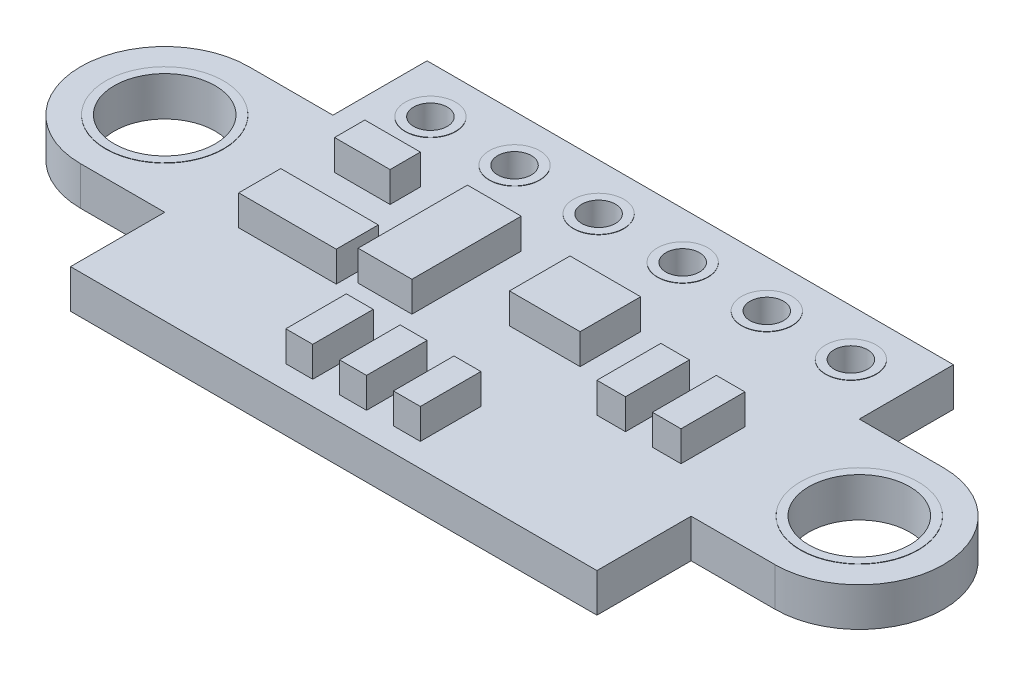
SolidWorks part; units mm, degrees
material "Copper"
ref_plane "Front Plane" through (0, 0, 0) normal (0, 0, 1) x (1, 0, 0)
ref_plane "Top Plane" through (0, 0, 0) normal (0, 1, 0) x (1, 0, 0)
ref_plane "Right Plane" through (0, 0, 0) normal (1, 0, 0) x (0, 0, -1)
sketch "Sketch1" plane through (0, 0, 0) normal (0, 1, 0) x (1, 0, 0)
  line L5 (-7.825, -5.3) -> (7.825, -5.3)
  line L6 (-7.825, -5.3) -> (-7.825, -2.5)
  line L7 (-7.825, 5.3) -> (7.825, 5.3)
  line L8 (7.825, -5.3) -> (7.825, -2.5)
  line L11 (10.325, 2.5) -> (7.825, 2.5)
  line L12 (10.325, -2.5) -> (7.825, -2.5)
  line L13 (-10.325, 2.5) -> (-7.825, 2.5)
  line L14 (-10.325, -2.5) -> (-7.825, -2.5)
  line L15 (-7.825, 2.5) -> (-7.825, 5.3)
  line L16 (7.825, 2.5) -> (7.825, 5.3)
  arc A0 (10.325, -2.5) -> (10.325, 2.5) centre (10.325, 0) ccw
  arc A1 (-10.325, -2.5) -> (-10.325, 2.5) centre (-10.325, 0) cw
  circle A2 centre (-10.325, 0) radius 1.5
  circle A3 centre (10.325, 0) radius 1.5
  point P0 (0, 0)
  dimension "D4" = 5
  dimension "D1" = 3
  dimension "D2" = 5
  dimension "D3" = 15.65
  dimension "D5" = 10.6
extrude "PCB" add sketch "Sketch1" along normal blind 1.15
sketch "Sketch2" plane through (0, 1.15, 0) normal (0, 1, 0) x (1, 0, 0)
  line L0 (-7.825, 3.9) -> (7.825, 3.9) construction
  line L1 (-7.825, 5.3) -> (-7.825, 2.5) construction
  line L2 (7.825, 2.5) -> (7.825, 5.3) construction
  circle A0 centre (-6.325, 3.9) radius 0.5
  dimension "D1" = 1
  dimension "D2" = 1.5
extrude "Initial Hole" cut sketch "Sketch2" against normal through all
pattern_linear "Pin Hole LPattern" count 6 spacing 2.5 along (1, 0, 0) of "Initial Hole"
sketch "Sketch4" plane through (0, 0, 0) normal (0, -1, 0) x (1, 0, 0)
  line L0 (-7.825, 2.5) -> (-7.825, 5.3) construction
  line L1 (-2.325, 3.7) -> (2.075, 3.7)
  line L2 (-2.325, 3.7) -> (-2.325, 1.3)
  line L3 (-2.325, 1.3) -> (2.075, 1.3)
  line L4 (2.075, 3.7) -> (2.075, 1.3)
  line L5 (-7.825, 5.3) -> (7.825, 5.3) construction
  dimension "D1" = 2.4
  dimension "D2" = 4.4
  dimension "D3" = 5.5
  dimension "D4" = 1.6
extrude "Bottom Component" add sketch "Sketch4" along normal blind 0.7
sketch "Sketch3" plane through (0, 1.15, 0) normal (0, 1, 0) x (1, 0, 0)
  line L0 (-1.325, -4.6) -> (-1.325, -2.8)
  line L1 (7.825, -5.3) -> (7.825, -2.5) construction
  line L2 (-6.325, -0.55) -> (-3.425, -0.55)
  line L3 (-6.325, -0.55) -> (-6.325, -1.8)
  line L4 (-6.325, -1.8) -> (-3.425, -1.8)
  line L5 (-2.125, -2.8) -> (-2.125, -4.6)
  line L6 (-3.425, -0.55) -> (-3.425, -1.8)
  line L7 (-2.125, -2.8) -> (-1.325, -2.8)
  line L8 (-2.125, -4.6) -> (-1.325, -4.6)
  line L9 (-7.825, -5.3) -> (7.825, -5.3) construction
  line L10 (-7.825, -2.5) -> (-7.825, -5.3) construction
  line L11 (-1.325, -2.8) -> (-0.525, -2.8) construction
  line L12 (0.275, -2.8) -> (1.075, -2.8) construction
  line L13 (-0.525, -2.8) -> (0.275, -2.8)
  line L14 (-0.525, -2.8) -> (-0.525, -4.6)
  line L15 (-0.525, -4.6) -> (0.275, -4.6)
  line L16 (0.275, -2.8) -> (0.275, -4.6)
  line L17 (-3.125, 1.8) -> (-1.525, 1.8)
  line L18 (1.075, -2.8) -> (1.875, -2.8)
  line L19 (1.075, -2.8) -> (1.075, -4.6)
  line L20 (1.075, -4.6) -> (1.875, -4.6)
  line L21 (1.875, -2.8) -> (1.875, -4.6)
  line L22 (-6.325, 1.95) -> (-4.675, 1.95)
  line L23 (-6.325, 1.95) -> (-6.325, 1.05)
  line L24 (-6.325, 1.05) -> (-4.675, 1.05)
  line L25 (-4.675, 1.95) -> (-4.675, 1.05)
  line L26 (-3.125, 1.8) -> (-3.125, -1.45)
  line L27 (-3.125, -1.45) -> (-1.525, -1.45)
  line L28 (-1.525, 1.8) -> (-1.525, -1.45)
  line L29 (0.225, 1.5) -> (2.325, 1.5)
  line L30 (0.225, 1.5) -> (0.225, -0.3)
  line L31 (0.225, -0.3) -> (2.325, -0.3)
  line L32 (2.325, 1.5) -> (2.325, -0.3)
  line L33 (3.825, 0.6) -> (4.675, 0.6)
  line L34 (3.825, 0.6) -> (3.825, -1.3)
  line L35 (3.825, -1.3) -> (4.675, -1.3)
  line L36 (4.675, 0.6) -> (4.675, -1.3)
  line L37 (5.475, 0.6) -> (6.325, 0.6)
  line L38 (5.475, 0.6) -> (5.475, -1.3)
  line L39 (5.475, -1.3) -> (6.325, -1.3)
  line L40 (6.325, 0.6) -> (6.325, -1.3)
  line L41 (7.825, 2.5) -> (7.825, 5.3) construction
  line L42 (-7.825, 5.3) -> (-7.825, 2.5) construction
  point P44 (-5.5, 1.95)
  dimension "D1" = 0.7
  dimension "D2" = 5.7
  dimension "D3" = 0.8
  dimension "D4" = 1.8
  dimension "D5" = 1.9
  dimension "D6" = 0.85
  dimension "D7" = 4
  dimension "D8" = 1.5
  dimension "D9" = 0.8
  dimension "D10" = 1.8
  dimension "D11" = 2.1
  dimension "D12" = 5.5
  dimension "D13" = 5
  dimension "D14" = 1.6
  dimension "D15" = 3.25
  dimension "D16" = 1.75
  dimension "D17" = 1.35
  dimension "D18" = 2.9
  dimension "D19" = 1.25
  dimension "D20" = 3.5
  dimension "D21" = 1.5
  dimension "D22" = 1.6
  dimension "D23" = 0.9
  dimension "D24" = 1.65
  dimension "D25" = 1.5
extrude "Tan Components" add sketch "Sketch3" along normal blind 0.9 contours L5 L8 L0 L7 | L16 L13 L14 L15 | L21 L18 L19 L20 | L25 L22 L23 L24 region at (-1.725, 1.15, 3.7) region at (-0.125, 1.15, 3.7) region at (1.475, 1.15, 3.7) region at (-5.5, 1.15, -1.5)
extrude "Black Components" add sketch "Sketch3<3>" along normal blind 0.9 contours L32 L29 L30 L31 | L28 L17 L26 L27 | L6 L2 L3 L4 | L36 L33 L34 L35 | L38 L39 L40 L37 region at (-4.875, 1.15, 1.175) region at (-2.325, 1.15, -0.175) region at (1.275, 1.15, -0.6) region at (4.25, 1.15, 0.35)
sketch "Sketch3<3>" plane through (0, 1.15, 0) normal (0, 1, 0) x (1, 0, 0) same geometry as "Sketch3"
sketch "Sketch5" plane through (0, 1.15, 0) normal (0, 1, 0) x (1, 0, 0)
  circle A0 centre (-10.325, 0) radius 1.75
  circle A1 centre (10.325, 0) radius 1.75
  circle A2 centre (-6.325, 3.9) radius 0.75
  circle A3 centre (-3.825, 3.9) radius 0.75
  circle A4 centre (-1.325, 3.9) radius 0.75
  circle A5 centre (1.175, 3.9) radius 0.75
  circle A6 centre (3.675, 3.9) radius 0.75
  circle A7 centre (6.175, 3.9) radius 0.75
  circle A8 centre (-6.325, 3.9) radius 0.5
  circle A9 centre (-3.825, 3.9) radius 0.5
  circle A10 centre (-1.325, 3.9) radius 0.5
  circle A11 centre (-1.325, 3.9) radius 0.5
  circle A12 centre (1.175, 3.9) radius 0.5
  circle A13 centre (3.675, 3.9) radius 0.5
  circle A14 centre (6.175, 3.9) radius 0.5
  circle A15 centre (-10.325, 0) radius 1.5
  circle A16 centre (10.325, 0) radius 1.5
  dimension "D1" = 3.5
  dimension "D2" = 1.5
  dimension "D3" = 1
  dimension "D4" = 3
extrude "Gold Contacts" add sketch "Sketch5" against normal offset from surface (1.17 mm away) 0.01 from offset 0.01 contours A2 A8 | A3 A9 | A4 A10 | A5 A12 | A6 A13 | A7 A14 | A0 A15 | A1 A16 region at (-12.0255, 1.15, 0) region at (8.6245, 1.15, 0) region at (-7.0538, 1.15, -3.9) region at (-4.5538, 1.15, -3.9) region at (-2.0538, 1.15, -3.9) region at (0.4462, 1.15, -3.9) region at (2.9462, 1.15, -3.9) region at (5.4462, 1.15, -3.9) up to face at (-3.825, 0, -3.4) offset beyond the face yes
sketch "Sketch6" plane through (0, 0, 0) normal (0, -1, 0) x (1, 0, 0)
  line L0 (-5.825, -2.8) -> (-5.825, 0.7) construction
  line L1 (-5.825, -2.8) -> (6.675, -2.8) construction
  line L2 (-3.325, -2.8) -> (-3.325, 0.7) construction
  line L3 (-0.825, -2.8) -> (-0.825, 0.7) construction
  line L4 (1.675, -2.8) -> (1.675, 0.7) construction
  line L5 (4.175, -2.8) -> (4.175, 0.7) construction
  line L6 (6.675, -2.8) -> (6.675, 0.7) construction
  line L8 (7.825, -5.3) -> (-7.825, -5.3) construction
  line L9 (7.825, -2.5) -> (7.825, -5.3) construction
  text T0 "VIN" font "Consolas" height 1
  text T1 "GND" font "Consolas" height 1
  text T2 "SCL" font "Consolas" height 1
  text T3 "SDA" font "Consolas" height 1
  text T4 "GPIO1" font "Consolas" height 1
  text T5 "XSHUT" font "Consolas" height 1
  dimension "D2" = 2.5
  dimension "D3" = 1.15
  dimension "D5" = 3.65
  dimension "D6" = 6.15
  dimension "D7" = 8.65
  dimension "D8" = 11.15
  dimension "D9" = 13.65
extrude "Silkscreen" add sketch "Sketch6" along normal blind 0.01
